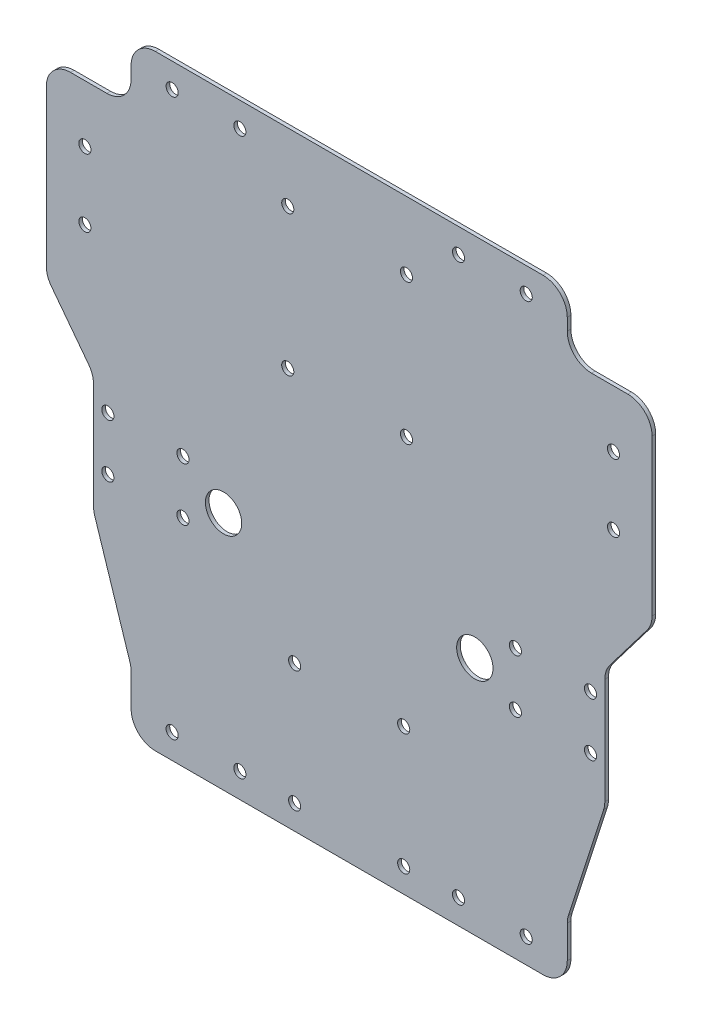
SolidWorks part; units mm, degrees
other "Markup1"
sketch "Sketch7" plane through (25, 0, 0) normal (-0.133, -0.1918, 0.9724) x (0.9904, 0.0125, 0.1379)
material "6061 Alloy"
ref_plane "Front Plane" through (0, 0, 0) normal (0, 0, 1) x (1, 0, 0)
ref_plane "Top Plane" through (0, 0, 0) normal (0, 1, 0) x (1, 0, 0)
ref_plane "Right Plane" through (0, 0, 0) normal (1, 0, 0) x (0, 0, -1)
sketch "Sketch1" plane through (0, 0, 0) normal (0, 0, 1) x (1, 0, 0)
  line L1 (0, 0) -> (300, 0)
  line L2 (0, 0) -> (0, 250)
  line L3 (0, 250) -> (300, 250)
  line L4 (300, 0) -> (300, 250)
  dimension "D1" = 300
  dimension "D2" = 250
extrude "Boss-Extrude1" add sketch "Sketch1" against normal blind 1.5
sketch "Motor Center Line" plane through (0, 0, -1.5) normal (0, 0, -1) x (-1, 0, 0)
  line L0 (0, 100) -> (-300, 100) construction
  line L3 (-300, 250) -> (0, 250) construction
  dimension "D1" = 150
sketch "Sketch2" plane through (0, 0, 0) normal (0, 0, 1) x (1, 0, 0)
  line L0 (150, 0.825) -> (150, -0.825) construction
  line L1 (0, 0) -> (20, 0)
  line L2 (0, 0) -> (0, 20)
  line L3 (0, 20) -> (20, 20)
  line L4 (20, 0) -> (20, 20)
  line L5 (300, 20) -> (280, 20)
  line L6 (280, 0) -> (280, 20)
  line L7 (300, 0) -> (280, 0)
  line L8 (300, 0) -> (300, 20)
  line L10 (0, 125) -> (300, 125) construction
  line L11 (0, 250) -> (0, 0) construction
  line L12 (300, 0) -> (300, 250) construction
  line L13 (300, 250) -> (300, 230)
  line L14 (300, 250) -> (280, 250)
  line L15 (280, 250) -> (280, 230)
  line L16 (300, 230) -> (280, 230)
  line L17 (0, 230) -> (20, 230)
  line L18 (20, 250) -> (20, 230)
  line L19 (0, 250) -> (20, 250)
  line L20 (0, 250) -> (0, 230)
  dimension "D1" = 20
sketch "Sketch3" plane through (0, 0, 0) normal (0, 0, 1) x (1, 0, 0)
  line L0 (150, 250) -> (150, 0) construction
  line L1 (0, 0) -> (25, 0)
  line L2 (0, 0) -> (0, 25)
  line L3 (0, 25) -> (25, 25)
  line L4 (25, 0) -> (25, 25)
  line L5 (300, 250) -> (0, 250) construction
  line L6 (0, 0) -> (300, 0) construction
  line L7 (0, 125) -> (300, 125) construction
  line L8 (0, 250) -> (0, 0) construction
  line L9 (300, 0) -> (300, 250) construction
  line L10 (300, 25) -> (275, 25)
  line L11 (275, 0) -> (275, 25)
  line L12 (300, 0) -> (275, 0)
  line L13 (300, 0) -> (300, 25)
  line L14 (300, 250) -> (300, 225)
  line L15 (300, 250) -> (275, 250)
  line L16 (275, 250) -> (275, 225)
  line L17 (300, 225) -> (275, 225)
  line L18 (0, 225) -> (25, 225)
  line L19 (25, 250) -> (25, 225)
  line L20 (0, 250) -> (25, 250)
  line L21 (0, 250) -> (0, 225)
  line L22 (255.5, 73) -> (275, 47.3437)
  line L23 (255.5, 73) -> (255.5, 121.6874)
  line L24 (255.5, 121.6874) -> (275, 147.3437)
  line L25 (275, 147.3437) -> (300, 147.3437)
  line L26 (300, 147.3437) -> (300, 25)
  line L27 (275, 47.3437) -> (275, 25)
  line L28 (44.5, 73) -> (25, 47.3437)
  line L29 (25, 47.3437) -> (25, 25)
  line L30 (44.5, 73) -> (44.5, 121.6874)
  line L31 (265.5, 121.25) -> (265.5, 78.75) construction
  line L32 (44.5, 121.6874) -> (25, 147.3437)
  line L37 (287.5, 147.3437) -> (287.5, 225)
  line L38 (25, 147.3437) -> (0, 147.3437)
  line L39 (12.5, 147.3437) -> (12.5, 225)
  circle A0 centre (201.85, 99.1258) radius 7.5
  circle A1 centre (98.15, 99.1258) radius 7.5
  ellipse E4 centre (201.85, 99.7743) end of major axis (201.2, 99.7743) minor radius 0.6484 construction
  line M15 (0, 250) -> (0, 0)
  line M16 (0, 0) -> (300, 0)
  line M17 (300, 0) -> (300, 250)
  line M18 (300, 250) -> (0, 250)
  dimension "D3" = 15
  dimension "D1" = 25
  dimension "D2" = 10
  dimension "D4" = 100
extrude "Cut-Extrude1" cut sketch "Sketch3" against normal through all both and the other way through all contours L11 L10 M16 M17 | L25 L24 L23 L10 M17 | L17 L16 M17 M18 | L19 L18 M18 M15 | L3 M15 | L4 L3 M16 M15 | A1 | A0 | L18 M15 | L37 L25 L17 M17 region at (12.5, 12.5, 0) region at (19.2941, 89.7643, 0) region at (287.5, 12.5, 0) region at (6.25, 186.1719, 0) region at (280.7059, 89.7643, 0) region at (12.5, 237.5, 0) region at (293.75, 186.1719, 0) region at (287.5, 237.5, 0) region at (201.85, 99.1258, 0) region at (98.15, 99.1258, 0)
sketch "Sketch4" plane through (0, 0, 0) normal (0, 0, 1) x (1, 0, 0)
  arc A0 (174.9953, 164.0221) -> (172.2953, 164.0221) centre (173.6453, 164.0221) ccw construction
  arc A1 (125.9953, 164.0221) -> (123.2953, 164.0221) centre (124.6453, 164.0221) ccw construction
  arc A4 (125.9953, 222.0221) -> (123.2953, 222.0221) centre (124.6453, 222.0221) ccw construction
  arc A5 (174.9953, 222.0221) -> (172.2953, 222.0221) centre (173.6453, 222.0221) ccw construction
  point P0 (40.9169, 201.47)
  point P1 (40.9169, 173.53)
  point P3 (76.94, 239.84)
  point P4 (104.88, 239.84)
  point P5 (195.12, 239.84)
  point P9 (223.06, 239.84)
  point P11 (259.0831, 201.47)
  point P13 (259.0831, 173.53)
  point P15 (195.12, 10.16)
  point P17 (223.06, 10.16)
  point P19 (76.94, 10.16)
  point P21 (104.88, 10.16)
  point P23 (127.5, 10)
  point P25 (172.5, 10)
  point P27 (127.5, 60)
  point P29 (172.5, 60)
  point P31 (124.6453, 164.0221)
  point P33 (173.6453, 164.0221)
  point P35 (124.6453, 222.0221)
  point P37 (173.6453, 222.0221)
  point P39 (218.6, 111)
  point P41 (249.6, 111)
  point P43 (249.6, 89)
  point P45 (218.6, 89)
  point P47 (81.4, 89.0063)
  point P49 (50.4, 89.0063)
  point P51 (81.4, 111.0063)
  point P53 (50.4, 111.0063)
sketch "Sketch6" plane through (0, 0, 0) normal (0, 0, 1) x (1, 0, 0)
  line L1 (275, 0) -> (240, 0)
  line L2 (275, 0) -> (275, 25)
  line L3 (275, 25) -> (240, 25)
  line L4 (240, 0) -> (240, 25)
  line L5 (240, 25) -> (255.5, 73)
  line L6 (150, 250) -> (150, 0) construction
  line L7 (275, 250) -> (25, 250) construction
  line L8 (25, 0) -> (275, 0) construction
  line L9 (60, 25) -> (44.5, 73)
  line L10 (25, 25) -> (60, 25)
  line L11 (60, 0) -> (60, 25)
  line L12 (25, 0) -> (60, 0)
  line L13 (25, 0) -> (25, 25)
  line L14 (275, 250) -> (240, 250)
  line L15 (25, 225) -> (60, 225)
  line L16 (25, 225) -> (25, 250)
  line L17 (25, 250) -> (60, 250)
  line L18 (60, 225) -> (60, 250)
  line L19 (240, 225) -> (240, 250)
  line L20 (275, 225) -> (240, 225)
  line L21 (275, 225) -> (275, 250)
  line L22 (25, 225) -> (25, 147.3437)
  line L23 (275, 147.3437) -> (275, 225)
  line L24 (287.5, 225) -> (287.5, 147.3437)
  line L25 (287.5, 147.3437) -> (275, 147.3437)
  line L26 (25, 225) -> (12.5, 225)
  line L27 (12.5, 225) -> (12.5, 147.3437)
  line L28 (12.5, 147.3437) -> (25, 147.3437)
  line M11 (275, 0) -> (275, 47.3437)
  line M12 (275, 47.3437) -> (255.5, 73)
  line M15 (275, 147.3437) -> (287.5, 147.3437)
  line M16 (287.5, 147.3437) -> (287.5, 225)
  line M17 (287.5, 225) -> (275, 225)
  line M18 (275, 225) -> (275, 250)
  line M19 (275, 250) -> (25, 250)
  line M20 (25, 250) -> (25, 225)
  line M21 (25, 225) -> (12.5, 225)
  line M22 (12.5, 225) -> (12.5, 147.3437)
  line M23 (12.5, 147.3437) -> (25, 147.3437)
  line M26 (44.5, 73) -> (25, 47.3437)
  line M27 (25, 47.3437) -> (25, 0)
  line M28 (25, 0) -> (275, 0)
  dimension "D1" = 25
  dimension "D2" = 35
extrude "Cut-Extrude3" cut sketch "Sketch6" against normal through all contours L11 L10 M28 M27 | L10 L9 M27 M26 | L4 L3 M28 M11 | L5 L3 M11 M12 | L15 L18 M19 M20 | L20 L19 M18 M19 | L22 M21 M22 M23 | L23 M15 M16 M17 region at (42.5, 12.5, 0) region at (257.5, 12.5, 0) region at (259.2359, 42.5338, 0) region at (40.7641, 42.5338, 0) region at (257.5, 237.5, 0) region at (281.25, 186.1719, 0) region at (18.75, 186.1719, 0) region at (42.5, 237.5, 0)
sketch "Sketch5" plane through (0, 0, 0) normal (0, 0, 1) x (1, 0, 0)
  circle A0 centre (76.94, 10.16) radius 2.5
  dimension "D1" = 5
extrude "Cut-Extrude2" cut sketch "Sketch5" against normal through all both
pattern_sketch "Sketch-Pattern1" of "Cut-Extrude2" driven by "Sketch4"
fillet "Fillet1" radius 10 16 edges at (255.5, 121.6874, -0.75) (44.5, 121.6874, -0.75) (240, 250, -0.75) (240, 225, -0.75) (60, 250, -0.75) (60, 225, -0.75) (44.5, 73, -0.75) (60, 25, -0.75) (60, 0, -0.75) (255.5, 73, -0.75) (240, 25, -0.75) (240, 0, -0.75) (275, 225, -0.75) (275, 147.3437, -0.75) (25, 225, -0.75) (25, 147.3437, -0.75)
